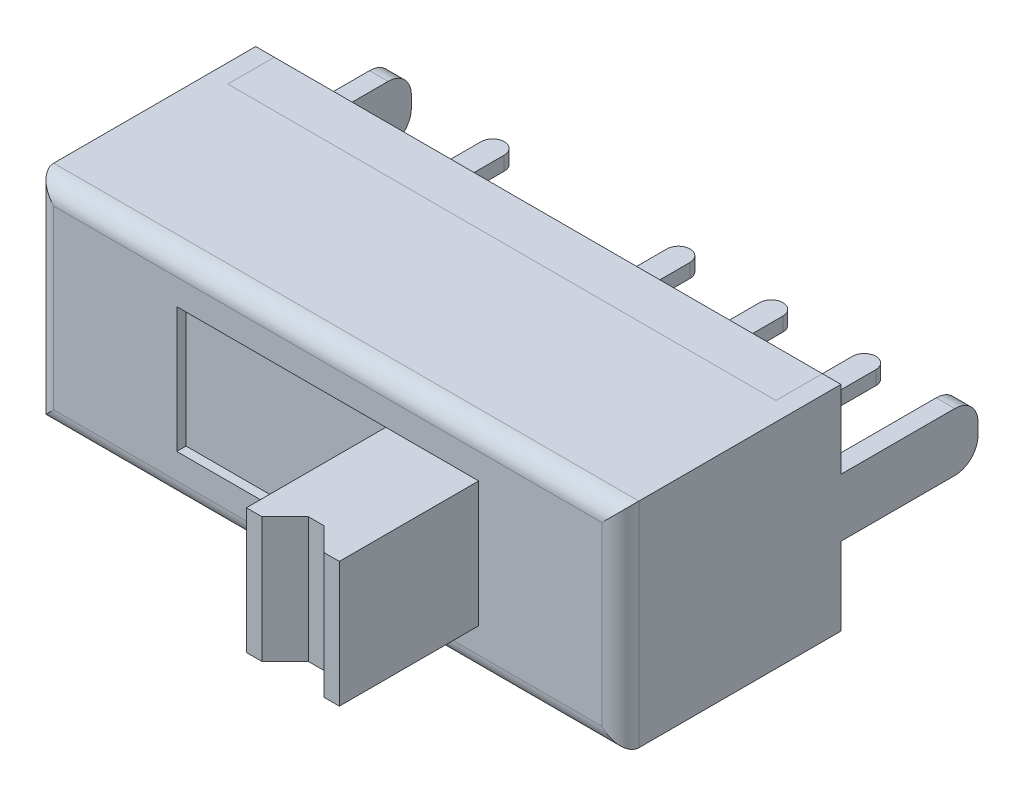
SolidWorks part; units mm, degrees
ref_plane "Front Plane" through (0, 0, 0) normal (0, 0, 1) x (1, 0, 0)
ref_plane "Top Plane" through (0, 0, 0) normal (0, 1, 0) x (1, 0, 0)
ref_plane "Right Plane" through (0, 0, 0) normal (1, 0, 0) x (0, 0, -1)
sketch "Sketch1" plane through (0, 0, 0) normal (0, 0, 1) x (1, 0, 0)
  line L1 (-6.3, 2.3) -> (6.3, 2.3)
  line L2 (-6.3, 2.3) -> (-6.3, -2.3)
  line L3 (-6.3, -2.3) -> (6.3, -2.3)
  line L4 (6.3, 2.3) -> (6.3, -2.3)
  line L5 (-6.3, 2.3) -> (6.3, -2.3) construction
  line L6 (-6.3, -2.3) -> (6.3, 2.3) construction
  point P0 (0, 0)
  dimension "D1" = 12.6
  dimension "D2" = 4.6
extrude "Boss-Extrude1" add sketch "Sketch1" along normal blind 4.75
fillet "Fillet2" radius 0.4 4 edges at (-6.3, 0, 4.75) (0, 2.3, 4.75) (6.3, 0, 4.75) (0, -2.3, 4.75)
sketch "Sketch2" plane through (0, 0, 4.75) normal (0, 0, 1) x (1, 0, 0)
  line L1 (-3.25, 1.35) -> (3.25, 1.35)
  line L2 (-3.25, 1.35) -> (-3.25, -1.35)
  line L3 (-3.25, -1.35) -> (3.25, -1.35)
  line L4 (3.25, 1.35) -> (3.25, -1.35)
  line L5 (-3.25, 1.35) -> (3.25, -1.35) construction
  line L6 (-3.25, -1.35) -> (3.25, 1.35) construction
  point P0 (0, 0)
  dimension "D1" = 2.7
  dimension "D2" = 6.5
extrude "Cut-Extrude1" cut sketch "Sketch2" against normal blind 0.2
sketch "Sketch4" plane through (0, -1.35, 0) normal (0, 1, 0) x (1, 0, 0)
  line L0 (3.25, -4.55) -> (3.25, -7.75)
  line L1 (3.25, -7.75) -> (2.9167, -7.75)
  line L2 (2.9167, -7.75) -> (2.4167, -7.25)
  line L3 (2.4167, -7.25) -> (2.0833, -7.25)
  line L4 (2.0833, -7.25) -> (1.5833, -7.75)
  line L5 (1.5833, -7.75) -> (1.25, -7.75)
  line L6 (1.25, -7.75) -> (1.25, -4.55)
  line L7 (3.25, -4.55) -> (-3.25, -4.55) construction
  line L8 (1.25, -4.55) -> (3.25, -4.55)
  line L9 (5.9, -4.75) -> (-5.9, -4.75) construction
  dimension "D1" = 2
  dimension "D2" = 3
  dimension "D3" = 45
  dimension "D4" = 0.5
extrude "Boss-Extrude2" add sketch "Sketch4" along normal up to surface (2.7 mm away) up to face at (0, 1.35, 4.65)
sketch "Sketch8" plane through (0, 0, 0) normal (0, 0, -1) x (-1, 0, 0)
  line L0 (-6.3, 2.3) -> (6.3, 2.3) construction
  line L1 (5.9, -2.3) -> (-5.9, -2.3)
  line L2 (5.9, -2.3) -> (5.9, 2.3)
  line L3 (5.9, 2.3) -> (-5.9, 2.3)
  line L4 (-5.9, -2.3) -> (-5.9, 2.3)
  line L5 (5.9, -2.3) -> (-5.9, 2.3) construction
  line L6 (5.9, 2.3) -> (-5.9, -2.3) construction
  line L7 (-6.3, -2.3) -> (-6.3, 2.3) construction
  point P0 (0, 0)
  dimension "D1" = 0.4
extrude "Cut-Extrude2" cut sketch "Sketch8" against normal blind 1
sketch "Sketch5" plane through (0, 0, 0) normal (0, 0, -1) x (-1, 0, 0)
  line L0 (-6.3, -2.3) -> (-6.3, 2.3) construction
  line L1 (-6.3, 0.625) -> (-5.9, 0.625)
  line L2 (-6.3, 0.625) -> (-6.3, -0.625)
  line L3 (-6.3, -0.625) -> (-5.9, -0.625)
  line L4 (-5.9, 0.625) -> (-5.9, -0.625)
  line L5 (0, 0) -> (-5.9, 0) construction
  dimension "D1" = 1.25
  dimension "D2" = 0.4
extrude "Boss-Extrude3" add sketch "Sketch5" along normal offset from surface (2.95 mm away) 7.7 up to face at (0.4167, 0, 4.75)
fillet "Fillet3" radius 0.5 2 edges at (6.1, -0.625, -2.95) (6.1, 0.625, -2.95)
mirror "Mirror1" about plane through (0, 0, 0) normal (1, 0, 0) of "Fillet3", "Boss-Extrude3"
sketch "Sketch10" plane through (0, 0, 1) normal (0, 0, -1) x (-1, 0, 0)
  line L1 (-0.25, 0.15) -> (0.25, 0.15)
  line L2 (-0.25, 0.15) -> (-0.25, -0.15)
  line L3 (-0.25, -0.15) -> (0.25, -0.15)
  line L4 (0.25, 0.15) -> (0.25, -0.15)
  line L5 (-0.25, 0.15) -> (0.25, -0.15) construction
  line L6 (-0.25, -0.15) -> (0.25, 0.15) construction
  point P0 (0, 0)
  dimension "D1" = 0.5
  dimension "D2" = 0.3
extrude "Boss-Extrude6" add sketch "Sketch10" along normal offset from surface (4.05 mm away) 7.8 up to face at (0.4167, 0, 4.75)
fillet "Fillet5" 2 edges at (0.25, 0, -3.05) (-0.25, 0, -3.05) type full round first side face at (0.25, 0, -1.025) second side face at (-0.25, 0, -1.025) middle face at (0, 0, -3.05)
pattern_linear "LPattern3" count 3 spacing 2 along (1, 0, 0) count 2 spacing 4 along (-1, 0, 0) of "Boss-Extrude6", "Fillet5" pattern seed only yes
sketch "Sketch9" plane through (0, 0, 1) normal (0, 0, -1) x (-1, 0, 0)
  line L1 (-5.9, 2.3) -> (5.9, 2.3)
  line L2 (-5.9, 2.3) -> (-5.9, -2.3)
  line L3 (-5.9, -2.3) -> (5.9, -2.3)
  line L4 (5.9, 2.3) -> (5.9, -2.3)
extrude "Boss-Extrude7" add sketch "Sketch9" along normal blind 1 separate body
